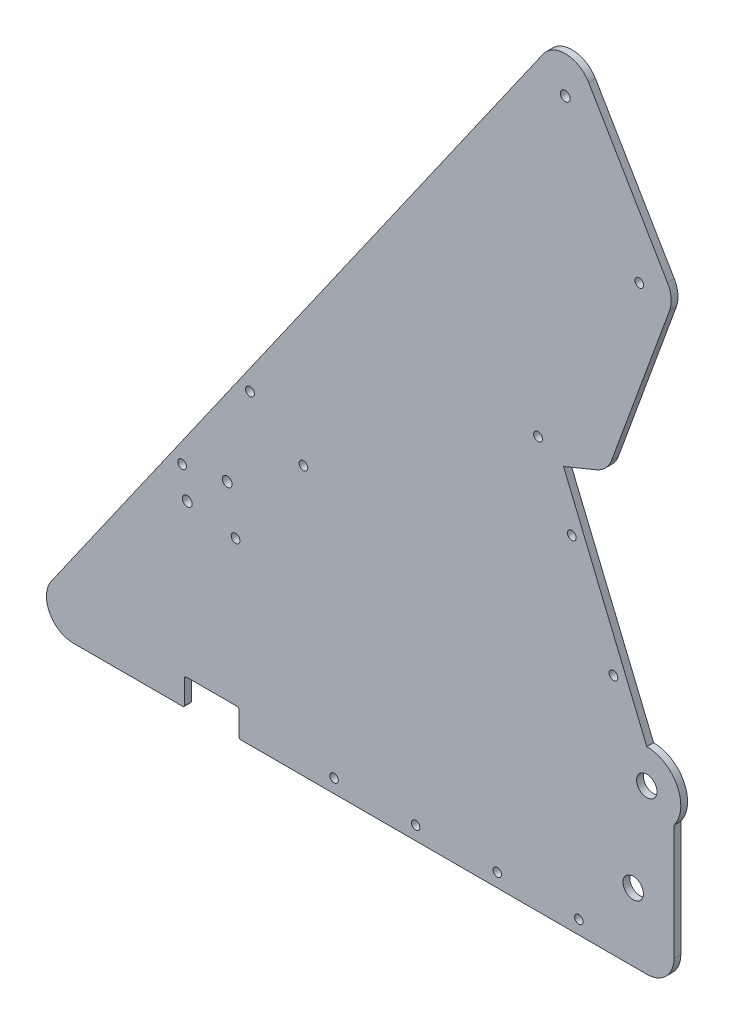
SolidWorks part; units mm, degrees
other "Markup1"
sketch "Sketch5"
ref_plane "Front Plane" through (0, 0, 0) normal (0, 0, 1) x (1, 0, 0)
ref_plane "Top Plane" through (0, 0, 0) normal (0, 1, 0) x (1, 0, 0)
ref_plane "Right Plane" through (0, 0, 0) normal (1, 0, 0) x (0, 0, -1)
sketch "Sketch1" plane through (0, 0, 0) normal (0, 0, 1) x (1, 0, 0)
  line L0 (0, 0) -> (76.2, 0)
  line L1 (304.8, 0) -> (304.8, 66.675)
  line L2 (254.9547, 364.1131) -> (0, 0)
  line L3 (304.8, 279.4) -> (254.9547, 364.1131)
  line L4 (76.2, 0) -> (76.2, 12.7)
  line L5 (76.2, 12.7) -> (101.6, 12.7)
  line L6 (101.6, 12.7) -> (101.6, 0)
  line L7 (101.6, 0) -> (304.8, 0)
  line L9 (292.1, 92.075) -> (253.2194, 185.9412)
  line L10 (253.2194, 185.9412) -> (273.7526, 194.4463)
  line L11 (273.7526, 194.4463) -> (304.8, 279.4)
  arc A0 (304.8, 66.675) -> (292.1, 92.075) centre (292.1, 76.2) ccw
  dimension "D7" = 12.7
  dimension "D8" = 76.2
  dimension "D10" = 31.75
  dimension "D1" = 304.8
  dimension "D2" = 279.4
  dimension "D3" = 55
  dimension "D4" = 444.5
  dimension "D5" = 76.2
  dimension "D6" = 25.4
  dimension "D9" = 292.1
  dimension "D11" = 101.6
  dimension "D12" = 22.5
  dimension "D13" = 22.225
extrude "Boss-Extrude1" add sketch "Sketch1" along normal blind 3.175
sketch "Sketch2" plane through (0, 0, 3.175) normal (0, 0, 1) x (1, 0, 0)
  line L0 (254.9547, 364.1131) -> (0, 0) construction
  line L1 (101.6, 0) -> (304.8, 0) construction
  line L2 (292.1, 92.075) -> (253.2194, 185.9412) construction
  line L3 (253.2194, 185.9412) -> (273.7526, 194.4463) construction
  line L4 (292.1, 92.075) -> (253.2194, 185.9412) construction
  line L5 (304.8, 279.4) -> (288.6002, 277.9261) construction
  line L6 (285.4785, 312.2373) -> (291.7219, 243.6149) construction
  line L7 (304.8, 279.4) -> (254.9547, 364.1131) construction
  line L8 (273.7526, 194.4463) -> (304.8, 279.4) construction
  line L9 (273.7526, 194.4463) -> (304.8, 279.4) construction
  circle A0 centre (77.4583, 84.0518) radius 2.286
  circle A1 centre (254, 336.1795) radius 2.286
  circle A2 centre (96.1158, 101.2872) radius 2.286
  circle A3 centre (257.0729, 160.0446) radius 2.032
  circle A4 centre (292.1, 76.2) radius 4.7625
  circle A5 centre (184.15, 6.35) radius 1.9682
  circle A6 centre (222.25, 6.35) radius 1.9682
  circle A7 centre (260.35, 6.35) radius 1.9682
  circle A8 centre (276.5132, 113.1115) radius 2.032
  circle A18 centre (288.6002, 277.9261) radius 2.032
  circle A26 centre (285.75, 31.75) radius 4.7625
  circle A28 centre (106.7599, 143.0587) radius 2.032
  circle A29 centre (106.7599, 143.0587) radius 2.032
  arc A30 (304.8, 66.675) -> (292.1, 92.075) centre (292.1, 76.2) ccw construction
  circle A31 centre (241.3, 192.0875) radius 2.032
  circle A34 centre (75.0727, 97.8047) radius 2.032
  circle A35 centre (75.0727, 97.8047) radius 2.032
  circle A37 centre (100.0405, 80.3221) radius 2.032
  circle A38 centre (100.0405, 80.3221) radius 2.032
  circle A39 centre (131.7277, 125.5761) radius 2.032
  circle A40 centre (131.7277, 125.5761) radius 2.032
  circle A41 centre (146.05, 6.35) radius 1.9682
  point P60 (288.6002, 277.9261)
  dimension "D3" = 4.572
  dimension "D5" = 4.572
  dimension "D9" = 4.572
  dimension "D14" = 3.9364
  dimension "D20" = 9.525
  dimension "D23" = 9.525
  dimension "D18" = 4.064
  dimension "D26" = 4.064
  dimension "D2" = 15.24
  dimension "D4" = 254
  dimension "D6" = 15.24
  dimension "D7" = 25.4
  dimension "D8" = 20.6375
  dimension "D15" = 146.05
  dimension "D16" = 6.35
  dimension "D21" = 44.45
  dimension "D22" = 6.35
  dimension "D19" = 160.3375
  dimension "D24" = 44.45
  dimension "D25" = 6.35
  dimension "D27" = 25.4
  dimension "D28" = 50.8
  dimension "D29" = 6.35
  dimension "D30" = 38.1
  dimension "D31" = 38.1
  dimension "D32" = 114.3
  dimension "D10" = 0.127
  dimension "D12" = 0.127
  dimension "D13" = 0.127
  dimension "D11" = 0.127
  dimension "D17" = 4
extrude "Cut-Extrude1" cut sketch "Sketch2" against normal through all
fillet "Fillet1" radius 12.7 5 edges at (0, 0, 1.5875) (304.8, 0, 1.5875) (254.9547, 364.1131, 1.5875) (273.7526, 194.4463, 1.5875) (304.8, 279.4, 1.5875)
fillet "Fillet2" radius 0.7937 4 edges at (101.6, 0, 1.5875) (101.6, 12.7, 1.5875) (76.2, 0, 1.5875) (76.2, 12.7, 1.5875)
equation "\"D6@Sketch2\"=\"D2@Sketch2\""
